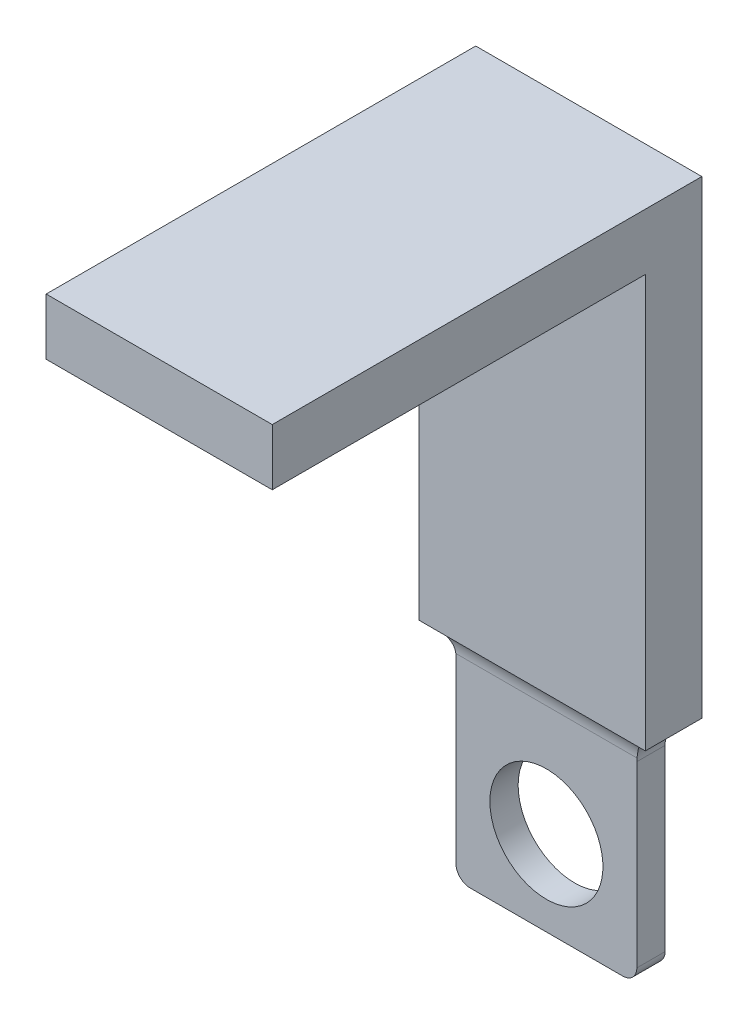
SolidWorks part; units mm, degrees
material "Czyste srebro"
ref_plane "Front Plane" through (0, 0, 0) normal (0, 0, 1) x (1, 0, 0)
ref_plane "Top Plane" through (0, 0, 0) normal (0, 1, 0) x (1, 0, 0)
ref_plane "Right Plane" through (0, 0, 0) normal (1, 0, 0) x (0, 0, -1)
sketch "Szkic1" plane through (0, 0, 0) normal (0, 1, 0) x (1, 0, 0)
  line L1 (0, 0) -> (-4, 0)
  line L2 (0, 0) -> (0, -1)
  line L3 (0, -1) -> (-4, -1)
  line L4 (-4, 0) -> (-4, -1)
  dimension "D1" = 1
  dimension "D2" = 4
extrude "Dodanie-wyciągnięcie1" add sketch "Szkic1" along normal blind 8.3 contours L1 L4 L3 L2
sketch "Szkic2" plane through (0, 0, 1) normal (0, 0, 1) x (1, 0, 0)
  line L0 (0, 8.3) -> (0, 0) construction
  line L1 (-4, 8.3) -> (0, 8.3)
  line L2 (-4, 8.3) -> (-4, 7.3)
  line L3 (-4, 7.3) -> (0, 7.3)
  line L4 (0, 8.3) -> (0, 7.3)
extrude "Dodanie-wyciągnięcie2" add sketch "Szkic2" along normal blind 6.6
sketch "Szkic3" plane through (0, 0, 0) normal (0, -1, 0) x (1, 0, 0)
  line L0 (-4, 0.5) -> (0, 0.5) construction
  line L1 (-4, 0) -> (-4, 1) construction
  line L2 (0, 0) -> (0, 1) construction
  line L4 (-3.6, 0.25) -> (-0.4, 0.25)
  line L5 (-3.6, 0.25) -> (-3.6, 0.75)
  line L6 (-3.6, 0.75) -> (-0.4, 0.75)
  line L7 (-0.4, 0.25) -> (-0.4, 0.75)
  line L8 (-3.6, 0.25) -> (-0.4, 0.75) construction
  line L9 (-3.6, 0.75) -> (-0.4, 0.25) construction
  point P6 (-2, 0.5)
  dimension "D1" = 0.5
extrude "Dodanie-wyciągnięcie3" add sketch "Szkic3" along normal blind 3.9
fillet "Zaokrąglenie1" radius 0.5 4 edges at (-2, 0, 0.75) (-3.6, 0, 0.5) (-2, 0, 0.25) (-0.4, 0, 0.5)
fillet "Zaokrąglenie2" radius 0.25 2 edges at (-0.4, -3.9, 0.5) (-3.6, -3.9, 0.5)
sketch "Szkic4" plane through (0, 0, 0.25) normal (0, 0, -1) x (-1, 0, 0)
  circle A0 centre (2, -2.3991) radius 1
extrude "Wytnij-wyciągnięcie1" cut sketch "Szkic4" against normal blind 3.9
